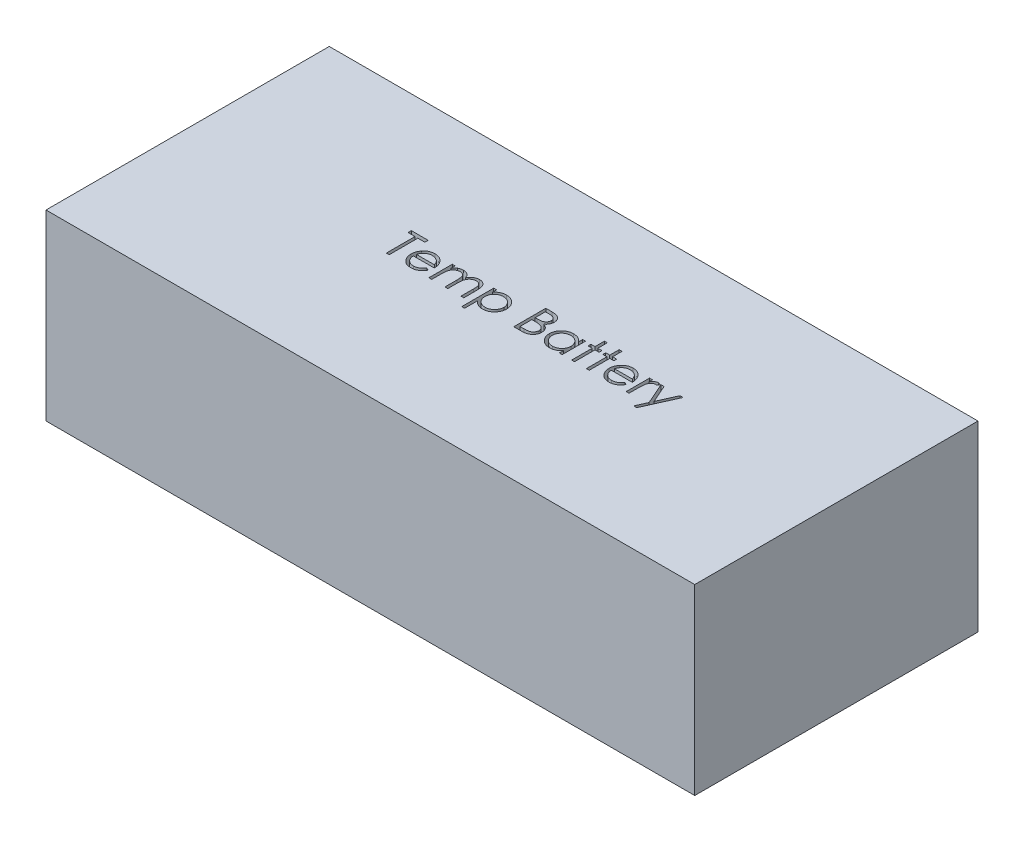
SolidWorks part; units mm, degrees
ref_plane "Front Plane" through (0, 0, 0) normal (0, 0, 1) x (1, 0, 0)
ref_plane "Top Plane" through (0, 0, 0) normal (0, 1, 0) x (1, 0, 0)
ref_plane "Right Plane" through (0, 0, 0) normal (1, 0, 0) x (0, 0, -1)
sketch "Sketch1" plane through (0, 0, 0) normal (0, 1, 0) x (1, 0, 0)
  line L1 (35.5, -15.5) -> (-35.5, -15.5)
  line L2 (35.5, -15.5) -> (35.5, 15.5)
  line L3 (35.5, 15.5) -> (-35.5, 15.5)
  line L4 (-35.5, -15.5) -> (-35.5, 15.5)
  line L5 (35.5, -15.5) -> (-35.5, 15.5) construction
  line L6 (35.5, 15.5) -> (-35.5, -15.5) construction
  point P0 (0, 0)
  dimension "D1" = 71
  dimension "D2" = 31
extrude "Boss-Extrude1" add sketch "Sketch1" along normal blind 20
sketch "Sketch2" plane through (0, 20, 0) normal (0, 1, 0) x (1, 0, 0)
  text T0 "Temp Battery"
extrude "Cut-Extrude1" cut sketch "Sketch2" against normal blind 4
